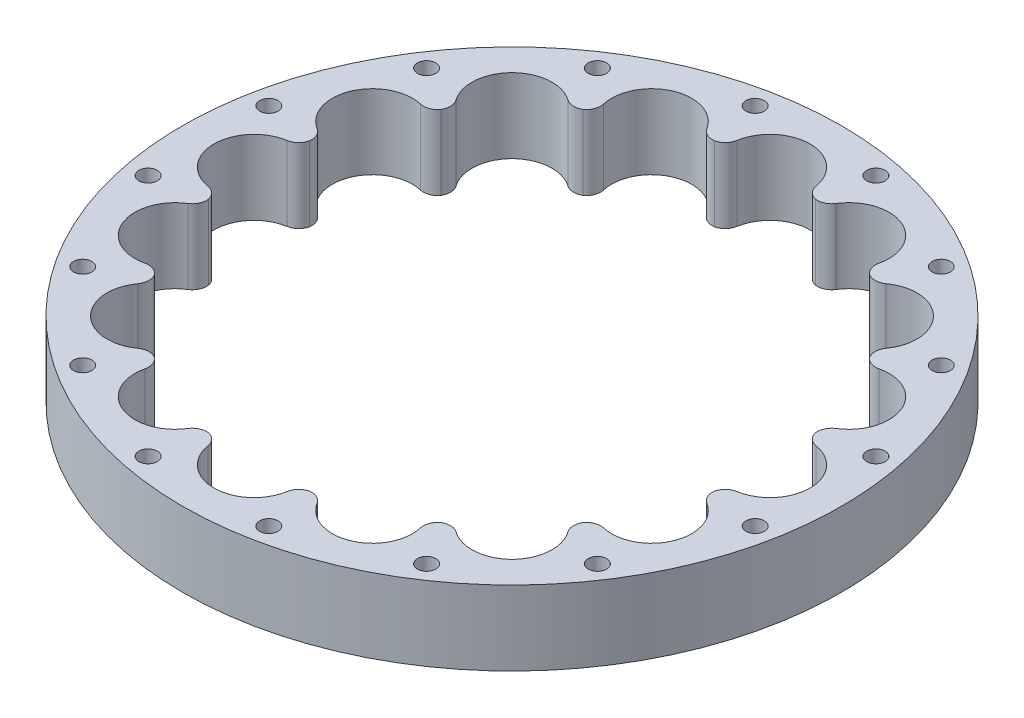
SolidWorks part; units mm, degrees
ref_plane "Front Plane" through (0, 0, 0) normal (0, 0, 1) x (1, 0, 0)
ref_plane "Top Plane" through (0, 0, 0) normal (0, 1, 0) x (1, 0, 0)
ref_plane "Right Plane" through (0, 0, 0) normal (1, 0, 0) x (0, 0, -1)
sketch "Sketch1" plane through (0, 0, 0) normal (0, 1, 0) x (1, 0, 0)
  line L0 (-10.5349, 52.9624) -> (0, 0) construction
  line L1 (0, 0) -> (-17.2208, 41.5746) construction
  circle A0 centre (0, 0) radius 45
  circle A1 centre (0, 45) radius 7
  circle A2 centre (17.2208, 41.5746) radius 7
  circle A3 centre (31.8198, 31.8198) radius 7
  circle A4 centre (41.5746, 17.2208) radius 7
  circle A5 centre (45, 0) radius 7
  circle A6 centre (41.5746, -17.2208) radius 7
  circle A7 centre (31.8198, -31.8198) radius 7
  circle A8 centre (17.2208, -41.5746) radius 7
  circle A9 centre (0, -45) radius 7
  circle A10 centre (-17.2208, -41.5746) radius 7
  circle A11 centre (-31.8198, -31.8198) radius 7
  circle A12 centre (0, 0) radius 57.5
  circle A13 centre (0, 0) radius 54 construction
  circle A14 centre (-10.5349, 52.9624) radius 1.6
  circle A15 centre (10.5349, 52.9624) radius 1.6
  circle A16 centre (30.0008, 44.8994) radius 1.6
  circle A17 centre (44.8994, 30.0008) radius 1.6
  circle A18 centre (52.9624, 10.5349) radius 1.6
  circle A19 centre (52.9624, -10.5349) radius 1.6
  circle A20 centre (44.8994, -30.0008) radius 1.6
  circle A21 centre (30.0008, -44.8994) radius 1.6
  circle A22 centre (10.5349, -52.9624) radius 1.6
  circle A23 centre (-10.5349, -52.9624) radius 1.6
  circle A24 centre (-30.0008, -44.8994) radius 1.6
  circle A25 centre (-44.8994, -30.0008) radius 1.6
  circle A26 centre (-41.5746, -17.2208) radius 7
  circle A27 centre (-45, 0) radius 7
  circle A28 centre (-41.5746, 17.2208) radius 7
  circle A29 centre (-31.8198, 31.8198) radius 7
  circle A30 centre (-17.2208, 41.5746) radius 7
  circle A31 centre (-52.9624, -10.5349) radius 1.6
  circle A32 centre (-52.9624, 10.5349) radius 1.6
  circle A33 centre (-44.8994, 30.0008) radius 1.6
  circle A34 centre (-30.0008, 44.8994) radius 1.6
  point P27 (0, 0)
  point P54 (0, 0)
  dimension "D1" = 90
  dimension "D2" = 14
  dimension "D4" = 115
  dimension "D5" = 108
  dimension "D6" = 3.2
  dimension "D8" = 11.25
  dimension "D3" = 16
  dimension "D7" = 16
extrude "Boss-Extrude1" add sketch "Sketch1" along normal blind 13 contours A12 A25 A24 A23 A22 A21 A20 A19 A18 A17 A16 A15 A14 A11 A0 A1 A2 A3 A4 A5 A6 A7 A8 A9 A10 region at (-55.8737, 0, 0)
fillet "Fillet1" radius 2.5 32 edges at (38.4009, 6.5, -23.46) (36.3696, 6.5, -26.5001) (44.4556, 6.5, -6.9788) (43.7422, 6.5, -10.5648) (44.4556, 6.5, 6.9788) (43.7422, 6.5, 10.5648) (38.4009, 6.5, 23.46) (36.3696, 6.5, 26.5001) (26.5001, 6.5, 36.3696) (23.46, 6.5, 38.4009) (6.9788, 6.5, 44.4556) (10.5648, 6.5, 43.7422) (-6.9788, 6.5, 44.4556) (-10.5648, 6.5, 43.7422) (-23.46, 6.5, 38.4009) (-26.5001, 6.5, 36.3696) (26.5001, 6.5, -36.3696) (23.46, 6.5, -38.4009) (10.5648, 6.5, -43.7422) (6.9788, 6.5, -44.4556) (-6.9788, 6.5, -44.4556) (-36.3696, 6.5, 26.5001) (-10.5648, 6.5, -43.7422) (-23.46, 6.5, -38.4009) (-26.5001, 6.5, -36.3696) (-36.3696, 6.5, -26.5001) (-38.4009, 6.5, -23.46) (-43.7422, 6.5, -10.5648) (-44.4556, 6.5, -6.9788) (-44.4556, 6.5, 6.9788) (-43.7422, 6.5, 10.5648) (-38.4009, 6.5, 23.46)
